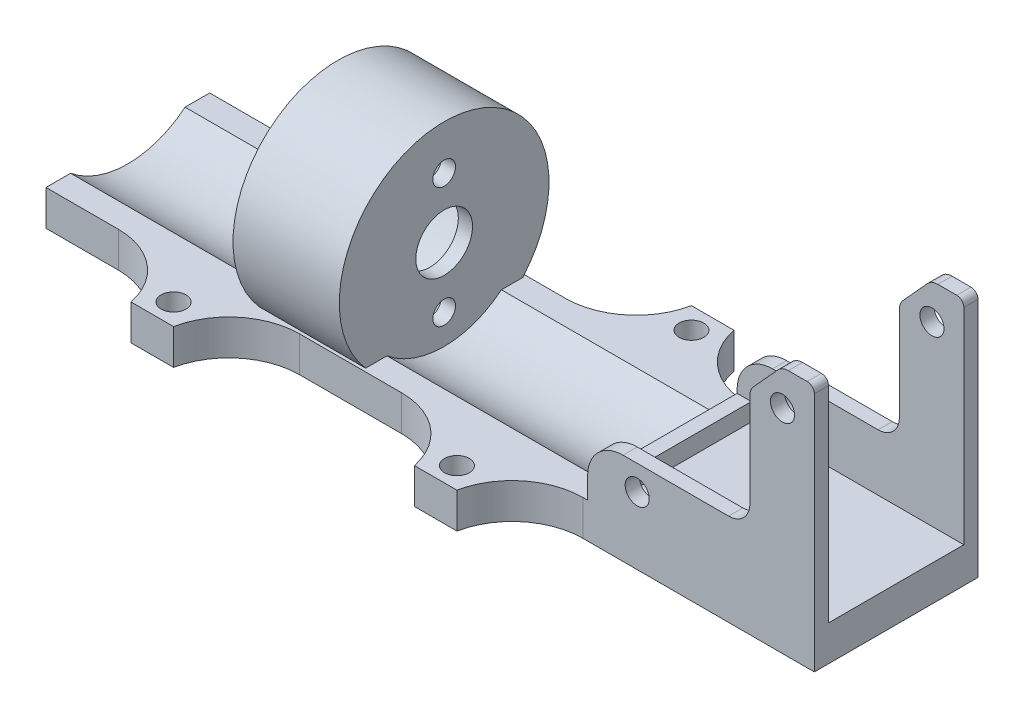
SolidWorks part; units mm, degrees
ref_plane "Front Plane" through (0, 0, 0) normal (0, 0, 1) x (1, 0, 0)
ref_plane "Top Plane" through (0, 0, 0) normal (0, 1, 0) x (1, 0, 0)
ref_plane "Right Plane" through (0, 0, 0) normal (1, 0, 0) x (0, 0, -1)
sketch "Sketch3" plane through (0, 0, 0) normal (0, 1, 0) x (1, 0, 0)
  line L0 (-20.2, 9.35) -> (-20.7, 9.35) construction
  line L1 (12, -11.55) -> (-99.3484, -11.55)
  line L2 (12, -11.55) -> (12, 11.55)
  line L3 (12, 11.55) -> (-99.3484, 11.55)
  line L4 (-99.3484, -11.55) -> (-99.3484, 11.55)
  line L5 (12, -11.55) -> (-99.3484, 11.55) construction
  line L6 (12, 11.55) -> (-99.3484, -11.55) construction
  line L7 (-20.7, 9.35) -> (-20.7, -9.35) construction
  line L8 (-20.7, -9.35) -> (-20.2, -9.35) construction
  line L9 (9.3, 9.35) -> (-20.2, 9.35) construction
  line L10 (9.8, 9.35) -> (9.3, 9.35) construction
  line L11 (9.3, -9.35) -> (9.8, -9.35) construction
  line L12 (9.8, -9.35) -> (9.8, 9.35) construction
  line L13 (9.3, -9.35) -> (-20.2, -9.35) construction
  line L14 (-20.2, 9.35) -> (-20.7, 9.35) construction
  line L15 (-20.7, 9.35) -> (-20.7, -9.35) construction
  line L16 (-20.7, -9.35) -> (-20.2, -9.35) construction
  line L17 (9.3, 9.35) -> (-20.2, 9.35) construction
  line L18 (9.8, 9.35) -> (9.3, 9.35) construction
  line L19 (9.3, -9.35) -> (9.8, -9.35) construction
  line L20 (9.8, -9.35) -> (9.8, 9.35) construction
  line L21 (9.3, -9.35) -> (-20.2, -9.35) construction
  line L22 (9.3, 9.55) -> (-20.2, 9.55)
  line L23 (-20.2, 9.55) -> (-20.9, 9.55)
  line L24 (-20.9, 9.55) -> (-20.9, -9.55)
  line L25 (-20.9, -9.55) -> (-20.2, -9.55)
  line L26 (9.3, -9.55) -> (-20.2, -9.55)
  line L27 (9.3, -9.55) -> (10, -9.55)
  line L28 (10, -9.55) -> (10, 9.55)
  line L29 (10, 9.55) -> (9.3, 9.55)
  line L30 (-22.9, -11.55) -> (-22.9, 11.55)
  point P0 (-43.6742, 0)
  dimension "D2" = 2
  dimension "D3" = 2
  dimension "D4" = 2
  dimension "D1" = 0.2
extrude "Boss-Extrude1" add sketch "Sketch3" against normal blind 5 contours L2 L3 L4 L1
extrude "Boss-Extrude2" add sketch "Sketch3<4>" along normal blind 2.5 contours L30 L1 L2 L3 L29 L28 L27 L26 L25 L24 L23 L22 region at (-5.45, 0, 11.1315)
sketch "Sketch3<4>" plane through (0, 0, 0) normal (0, 1, 0) x (1, 0, 0) same geometry as "Sketch3"
ref_plane "Plane1" through (-53.7, 0, 0) normal (1, 0, 0) x (0, 0, -1)
sketch "Sketch4" plane through (-53.7, 0, 0) normal (1, 0, 0) x (0, 0, -1)
  circle A0 centre (0, 9.8) radius 12.7
  circle A1 centre (0, 9.8) radius 14.8
  circle A2 centre (0, 1.3) radius 1.6
  circle A3 centre (0, 18.3) radius 1.6
  circle A4 centre (0, 9.8) radius 4
  circle A5 centre (0, 9.8) radius 17
  dimension "D1" = 25.4
  dimension "D2" = 29.6
  dimension "D3" = 8
  dimension "D4" = 34
  dimension "D5" = 3.2
  dimension "D6" = 8.5
  dimension "D7" = 8.5
ref_plane "Plane2" through (-56.7, 0, 0) normal (1, 0, 0) x (0, 0, -1)
extrude "Cut-Extrude1" cut sketch "Sketch4<4>" against normal through all and the other way up to surface (30.8 mm away) contours A0 A4 A3 A2 | A3 | A4 | A2 region at (-53.7, 9.8, 12.3408) other way up to face at (-22.9, 1.25, 0)
sketch "Sketch4<4>" plane through (-53.7, 0, 0) normal (1, 0, 0) x (0, 0, -1) same geometry as "Sketch4"
extrude "Boss-Extrude3" add sketch "Sketch4" along normal blind 2 from offset 3 contours A0 A4 A3 A2 region at (-53.7, 9.8, 12.3408) offset against normal yes
extrude "Boss-Extrude4" add sketch "Sketch4<3>" along normal blind 2 and the other way blind 13 from offset 3 contours A1 A0 region at (-53.7, 9.8, 14.3814) offset against normal yes
sketch "Sketch4<3>" plane through (-53.7, 0, 0) normal (1, 0, 0) x (0, 0, -1) same geometry as "Sketch4"
sketch "Sketch5" plane through (0, 0, 0) normal (0, 1, 0) x (1, 0, 0)
  line L13 (-99.3484, -11.55) -> (-99.3484, -8.0777) construction
  line L19 (12, -11.55) -> (-22.9, -11.55) construction
  line L21 (-42.4984, -16.15) -> (-42.4984, -11.55)
  line L22 (-42.4984, -11.55) -> (-51.6984, -11.55)
  line L23 (-51.6984, -11.55) -> (-51.6984, -16.15)
  line L25 (-66.6984, -16.15) -> (-66.6984, -11.55)
  line L26 (-66.6984, -11.55) -> (-75.8984, -11.55)
  line L27 (-75.8984, -11.55) -> (-75.8984, -16.15)
  line L28 (-22.9, -11.55) -> (-99.3484, -11.55) construction
  line L29 (-66.6984, -11.55) -> (-99.3484, -11.55) construction
  circle A1 centre (-47.0984, -16.15) radius 4.6
  circle A2 centre (-47.0984, -16.15) radius 1.6
  circle A3 centre (-71.2984, -16.15) radius 4.6
  circle A4 centre (-71.2984, -16.15) radius 1.6
  line M4 (-99.3484, -11.55) -> (-22.9, -11.55)
  dimension "D1" = 3
  dimension "D2" = 3.2
  dimension "D4" = 3.2
  dimension "D3" = 3
  dimension "D5" = 15
  dimension "D6" = 23.45
extrude "Boss-Extrude5" [suppressed] add sketch "Sketch5" against normal up to surface (5 mm away) contours A1 A2 | A1 L22 L23 | A1 L21 L22 | A3 A4 | A3 L27 M4 | A3 L25 L26
sketch "Sketch6" plane through (0, 0, 0) normal (0, 0, 1) x (1, 0, 0)
  line L0 (-20.9, 8.1477) -> (-20.9, -10.9145) construction
  line L1 (-22.9, 2.5) -> (-22.9, 0) construction
  line L2 (4.6, 31.3337) -> (4.6, -13.4879) construction
  line L4 (-22.9, 2.5) -> (-22.9, 3)
  line L5 (-15.9, 10.9933) -> (-15.9, -13.4879) construction
  line L6 (-25.4473, 0) -> (15.9611, 0) construction
  line L8 (12, 2.5) -> (-22.9, 2.5) construction
  line L17 (-22.9, 2.5) -> (10, 2.5)
  line L18 (-17.9, 8) -> (-8.9, 8)
  line L24 (12, 2.5) -> (12, 29)
  line L25 (11, 30) -> (1, 30)
  line L26 (0, 29) -> (0, 8)
  line L27 (0, 8) -> (-8.9, 8)
  line L28 (12, 2.5) -> (12, 0)
  line L29 (12, -5) -> (12, 2.5) construction
  line L30 (12, 0) -> (10, 0)
  line L31 (10, 0) -> (10, 2.5)
  circle A0 centre (-15.9, 4.5) radius 1.7
  arc A4 (-22.9, 3) -> (-17.9, 8) centre (-17.9, 3) cw
  arc A5 (12, 29) -> (11, 30) centre (11, 29) ccw
  arc A6 (1, 30) -> (0, 29) centre (1, 29) ccw
  circle A7 centre (4.6, 25) radius 1.7
  dimension "D1" = 2
  dimension "D3" = 5
  dimension "D4" = 2.5
  dimension "D5" = 3.4
  dimension "D8" = 5.5
  dimension "D11" = 3.4
  dimension "D12" = 5
  dimension "D13" = 5
  dimension "D14" = 25.5
  dimension "D10" = 1
  dimension "D2" = 25.5
  dimension "D6" = 4.5
  dimension "D7" = 27.5
  dimension "D9" = 12
  dimension "D15" = 2
extrude "Boss-Extrude6" add sketch "Sketch6" along normal up to surface and the other way up to surface up to face at (-36.7495, -0.8333, 11.55) other way up to face at (-36.7495, -0.8333, -11.55)
ref_plane "Plane3" through (0, 0, -9.55) normal (0, 0, 1) x (1, 0, 0)
ref_plane "Plane4" through (0, 0, 9.55) normal (0, 0, -1) x (-1, 0, 0)
extrude "Cut-Extrude5" cut sketch "Sketch6<9>" against normal up to surface (9.55 mm away) and the other way up to surface (9.55 mm away) up to plane "Plane3" other way up to plane "Plane4"
sketch "Sketch6<9>" plane through (0, 0, 0) normal (0, 0, 1) x (1, 0, 0) same geometry as "Sketch6"
mirror "Mirror1" [suppressed] about plane through (0, 0, 0) normal (0, 0, 1)
fillet "Fillet1" radius 3 2 edges at (0, 8, 10.55) (0, 8, -10.55)
sketch "Sketch7" plane through (0, -5, 0) normal (0, -1, 0) x (1, 0, 0)
  line L0 (-54.7, -13.5331) -> (-54.7, 21.0401) construction
  line L5 (-54.7, -14.8) -> (-54.7, 14.8) construction
  line L6 (-105.0629, 0) -> (-9.1488, 0) construction
  circle A0 centre (-50.7, 6) radius 1
  circle A1 centre (-37.7, 6) radius 1
  circle A2 centre (-37.7, -6) radius 1
  circle A3 centre (-50.7, -6) radius 1
  dimension "D4" = 2
  dimension "D5" = 2
  dimension "D1" = 6
  dimension "D2" = 4
  dimension "D3" = 13
extrude "Cut-Extrude6" [suppressed] cut sketch "Sketch7" against normal up to surface (3.1257 mm away)
sketch "Sketch9" [suppressed] plane through (0, 0, 0) normal (0, 1, 0) x (1, 0, 0)
  circle A0 centre (-50.7, 6) radius 2.1
  circle A1 centre (-37.7, 6) radius 2.1
  circle A2 centre (-37.7, -6) radius 2.1
  circle A3 centre (-50.7, -6) radius 2.1
  dimension "D1" = 4.2
  dimension "D2" = 4.2
  dimension "D3" = 4.2
  dimension "D4" = 4.2
extrude "Cut-Extrude7" [suppressed] cut sketch "Sketch9" against normal blind 3
sketch "Sketch10" plane through (0, -5, 0) normal (0, -1, 0) x (1, 0, 0)
  line L0 (14.4706, 0) -> (-29.2059, 0) construction
  line L1 (12, -7) -> (12, 7)
  line L2 (12, 7) -> (-2, 7)
  line L3 (-2, 7) -> (-2, -7)
  line L4 (12, 11.55) -> (12, -11.55) construction
  line L5 (12, -7) -> (-2, -7)
  point P10 (12, 0)
  point P11 (-2, 0)
  dimension "D1" = 0
  dimension "D2" = 7
  dimension "D3" = 14
extrude "Boss-Extrude7" [suppressed] add sketch "Sketch10" along normal blind 0.7 contours L3 L5 L1 L2
sketch "Sketch11" [suppressed] plane through (0, -5, 0) normal (0, -1, 0) x (1, 0, 0)
  line L0 (-2, 0) -> (10.3358, 0) construction
  line L3 (-2, 7) -> (-2, -7) construction
  line L4 (5, 7) -> (5, 0) construction
  line L6 (12, 7) -> (-2, 7) construction
  circle A0 centre (5, 0) radius 2.05
  dimension "D1" = 4.1
extrude "Cut-Extrude8" [suppressed] cut sketch "Sketch11" against normal through all both and the other way through all
sketch "Sketch12" plane through (12, 0, 0) normal (1, 0, 0) x (0, 0, -1)
  line L0 (-14.4789, 32.9522) -> (-14.4789, -8.4719)
  line L1 (-14.4789, -8.4719) -> (16.7068, -8.4719)
  line L2 (16.7068, -8.4719) -> (16.7068, 32.9522)
  line L3 (16.7068, 32.9522) -> (-14.4789, 32.9522)
extrude "Cut-Extrude9" cut sketch "Sketch12" against normal blind 2.9
fillet "Fillet2" radius 1 2 edges at (9.1, 30, -10.55) (9.1, 30, 10.55)
sketch "Sketch13" plane through (0, 0, -11.55) normal (0, 0, -1) x (-1, 0, 0)
  line L1 (-4.55, 30) -> (0, 25)
  line L2 (-8.1, 30) -> (-1, 30) construction
  line L3 (0, 29) -> (0, 11) construction
  line L4 (-4.55, 30) -> (0, 30)
  line L5 (0, 30) -> (0, 25)
  dimension "D1" = 5
extrude "Cut-Extrude10" cut sketch "Sketch13" against normal through all
fillet "Fillet3" radius 2 4 edges at (4.55, 30, 10.55) (0, 25, 10.55) (0, 25, -10.55) (4.55, 30, -10.55)
sketch "Sketch14" plane through (0, -5, 0) normal (0, -1, 0) x (1, 0, 0)
  line L0 (9.1, 0) -> (-99.3484, 0) construction
  line L1 (-99.3484, 11.55) -> (-93.3484, 11.55) construction
  line L2 (-99.3484, 11.55) -> (-99.3484, 19.55) construction
  line L3 (-99.3484, 19.55) -> (-93.3484, 19.55) construction
  line L4 (-93.3484, 11.55) -> (-93.3484, 19.55) construction
  line L5 (9.1, -9.55) -> (9.1, 9.55) construction
  line L6 (-99.3484, 8.0777) -> (-99.3484, -8.0777) construction
  line L7 (-99.3484, -19.55) -> (-93.3484, -19.55) construction
  line L8 (-93.3484, -11.55) -> (-93.3484, -19.55) construction
  line L9 (-99.3484, -11.55) -> (-93.3484, -11.55) construction
  line L10 (-99.3484, -11.55) -> (-99.3484, -19.55) construction
  line L11 (-79.3484, -19.55) -> (-73.3484, -19.55)
  line L12 (-73.3484, -11.55) -> (-73.3484, -19.55)
  line L13 (-79.3484, -11.55) -> (-73.3484, -11.55)
  line L14 (-79.3484, -11.55) -> (-79.3484, -19.55)
  line L15 (-79.3484, 11.55) -> (-79.3484, 19.55)
  line L16 (-79.3484, 11.55) -> (-73.3484, 11.55)
  line L17 (-73.3484, 11.55) -> (-73.3484, 19.55)
  line L18 (-79.3484, 19.55) -> (-73.3484, 19.55)
  line L19 (-96.3484, -16.55) -> (-76.3484, -16.55) construction
  line L20 (-39.3484, -19.55) -> (-33.3484, -19.55)
  line L21 (-33.3484, -11.55) -> (-33.3484, -19.55)
  line L22 (-39.3484, -11.55) -> (-33.3484, -11.55)
  line L23 (-39.3484, -11.55) -> (-39.3484, -19.55)
  line L24 (-39.3484, 11.55) -> (-39.3484, 19.55)
  line L25 (-39.3484, 11.55) -> (-33.3484, 11.55)
  line L26 (-33.3484, 11.55) -> (-33.3484, 19.55)
  line L27 (-39.3484, 19.55) -> (-33.3484, 19.55)
  line L28 (-96.3484, -16.55) -> (-36.3484, -16.55) construction
  circle A0 centre (-96.3484, 16.55) radius 1.75 construction
  circle A1 centre (-96.3484, 16.55) radius 3 construction
  circle A2 centre (-96.3484, -16.55) radius 1.75 construction
  circle A3 centre (-76.3484, -16.55) radius 1.75
  circle A4 centre (-76.3484, 16.55) radius 1.75
  circle A5 centre (-36.3484, -16.55) radius 1.75
  circle A6 centre (-36.3484, 16.55) radius 1.75
  dimension "D1" = 3.5
  dimension "D4" = 6
  dimension "D2" = 3
  dimension "D3" = 6
  dimension "D5" = 5
  dimension "D6" = 3
  dimension "D7" = 2
  dimension "D8" = 20
  dimension "D10" = 60
  dimension "D9" = 2
extrude "Boss-Extrude8" add sketch "Sketch14" against normal up to surface (5 mm away) up to face at (-61.6621, 0, -9.699)
fillet "Fillet4" radius 10 8 edges at (-39.3484, -2.5, -11.55) (-33.3484, -2.5, -11.55) (-73.3484, -2.5, -11.55) (-79.3484, -2.5, -11.55) (-39.3484, -2.5, 11.55) (-33.3484, -2.5, 11.55) (-73.3484, -2.5, 11.55) (-79.3484, -2.5, 11.55)
